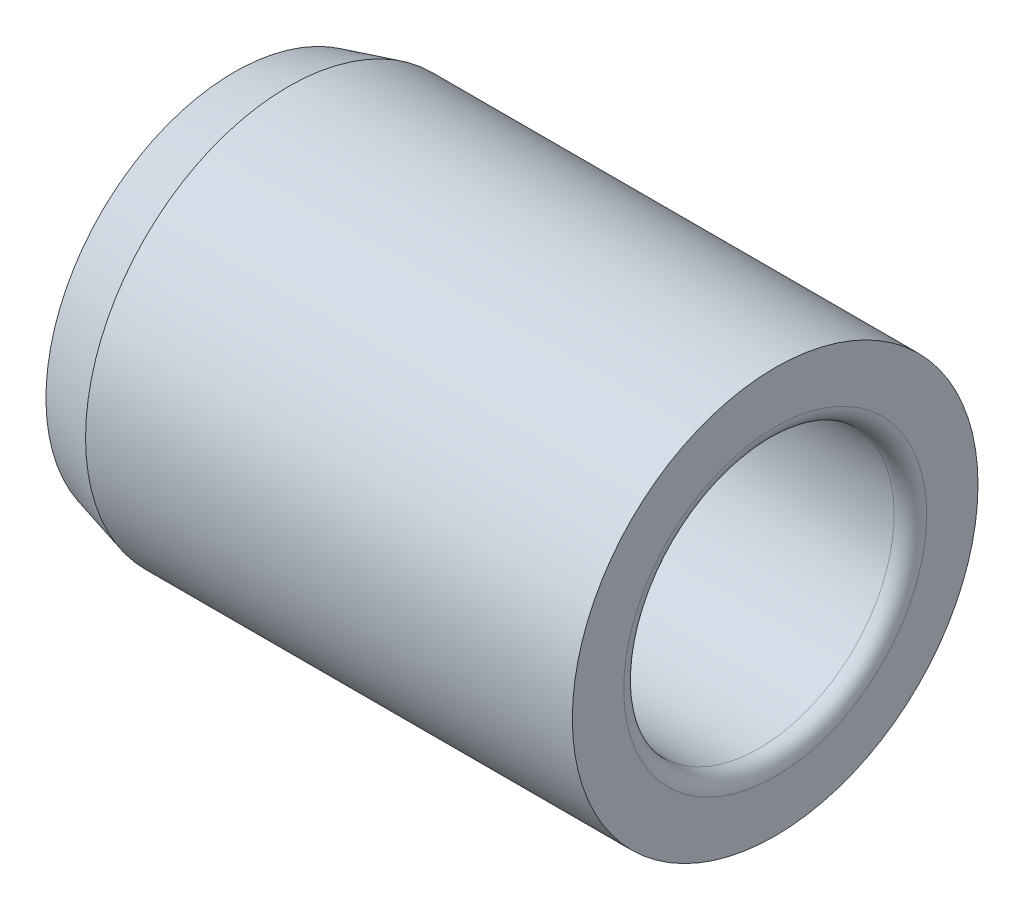
SolidWorks part; units mm, degrees
ref_plane "Front" through (0, 0, 0) normal (0, 0, 1) x (1, 0, 0)
ref_plane "Top" through (0, 0, 0) normal (0, 1, 0) x (1, 0, 0)
ref_plane "Right" through (0, 0, 0) normal (1, 0, 0) x (0, 0, -1)
sketch "Sketch1" plane through (0, 0, 0) normal (0, 0, 1) x (1, 0, 0)
  line L0 (-12.7, 0) -> (12.7, 0) construction
  line L1 (-12.7, 8.8444) -> (-10.16, 9.525)
  line L2 (-10.16, 9.525) -> (12.7, 9.525)
  line L3 (-12.7, 8.8444) -> (-12.7, 6.35)
  line L4 (-12.7, 6.35) -> (11.938, 6.35)
  line L5 (12.7, 9.525) -> (12.7, 7.112)
  arc A0 (11.938, 6.35) -> (12.7, 7.112) centre (11.938, 7.112) ccw
  point P2 (0, 0)
  point P11 (12.7, 6.35)
  dimension "D3" = 0.762
  dimension "D1" = 15
  dimension "D2" = 2.54
revolve "Revolve1" add sketch "Sketch1" angle 360 about L0
ref_axis "Center Axis 1" through (11.938, 0, 0) along (-1, 0, 0)
ref_plane "Contact Plane 1" through (-12.7, 0, 0) normal (-1, 0, 0) x (0, 0, 1)
ref_plane "Contact Plane 2" through (12.7, 0, 0) normal (1, 0, 0) x (0, 0, -1)
equation "\"D2@Sketch1\"=\"Length@Sketch1\"*.1"
equation "\"D3@Sketch1\"=\"Length@Sketch1\"*.03"
